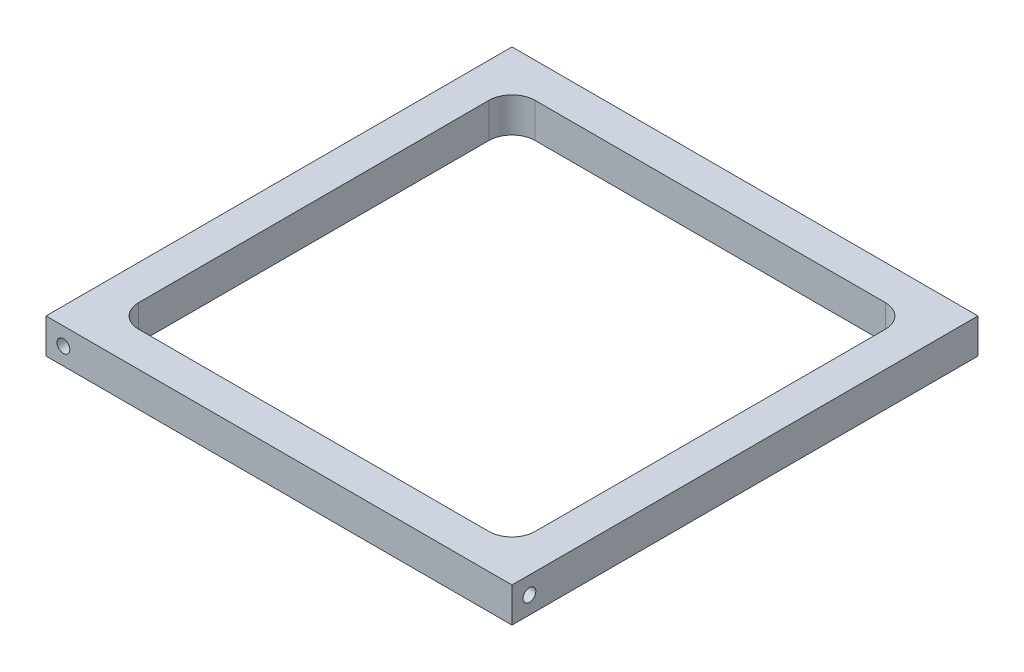
SolidWorks part; units mm, degrees
material "6061-T6 (SS)"
ref_plane "Front Plane" through (0, 0, 0) normal (0, 0, 1) x (1, 0, 0)
ref_plane "Top Plane" through (0, 0, 0) normal (0, 1, 0) x (1, 0, 0)
ref_plane "Right Plane" through (0, 0, 0) normal (1, 0, 0) x (0, 0, -1)
sketch "Sketch1" plane through (0, 0, 0) normal (0, 1, 0) x (1, 0, 0)
  line L5 (0, 0) -> (127.635, 0)
  line L6 (0, 0) -> (0, 127.635)
  line L7 (0, 127.635) -> (127.635, 127.635)
  line L8 (127.635, 0) -> (127.635, 127.635)
  dimension "D1" = 127.635
  dimension "D2" = 127.635
extrude "Boss-Extrude1" add sketch "Sketch1" along normal blind 9.525 contours L5 L8 L7 L6
sketch "Sketch5" plane through (0, 9.525, 0) normal (0, 1, 0) x (1, 0, 0)
  line L0 (63.8175, 127.635) -> (63.8175, 0) construction
  line L1 (0, 127.635) -> (127.635, 127.635) construction
  line L2 (0, 0) -> (127.635, 0) construction
  line L4 (9.525, 118.11) -> (118.11, 118.11)
  line L5 (9.525, 118.11) -> (9.525, 9.525)
  line L6 (9.525, 9.525) -> (118.11, 9.525)
  line L7 (118.11, 118.11) -> (118.11, 9.525)
  line L8 (9.525, 118.11) -> (118.11, 9.525) construction
  line L9 (9.525, 9.525) -> (118.11, 118.11) construction
  point P6 (63.8175, 63.8175)
  dimension "D1" = 108.585
  dimension "D2" = 108.585
extrude "Cut-Extrude1" cut sketch "Sketch5" against normal blind 9.525 contours L5 L4 L7 L6
fillet "Fillet1" radius 6.35 4 edges at (118.11, 4.7625, -9.525) (118.11, 4.7625, -118.11) (9.525, 4.7625, -118.11) (9.525, 4.7625, -9.525)
sketch "Sketch6" plane through (127.635, 0, 0) normal (1, 0, 0) x (0, 0, -1)
  circle A0 centre (4.7625, 4.7625) radius 1.7526
  dimension "D1" = 3.5052
extrude "6-32 hole1" cut sketch "Sketch6" against normal blind 6.35
sketch "Sketch7" plane through (0, 0, -127.635) normal (0, 0, -1) x (-1, 0, 0)
  circle A0 centre (-122.8725, 4.7625) radius 1.7526
  dimension "D1" = 3.5052
sketch "Sketch8" plane through (0, 0, 0) normal (-1, 0, 0) x (0, 0, 1)
  circle A0 centre (-122.8725, 4.7625) radius 1.7526
  dimension "D1" = 3.5052
sketch "Sketch9" plane through (0, 0, 0) normal (0, 0, 1) x (1, 0, 0)
  circle A0 centre (4.7625, 4.7625) radius 1.7526
  dimension "D1" = 3.5052
extrude "6-32 hole2" cut sketch "Sketch7" against normal blind 6.35
extrude "6-32 hole3" cut sketch "Sketch8" against normal blind 6.35
extrude "6-32 hole4" cut sketch "Sketch9" against normal blind 6.35
